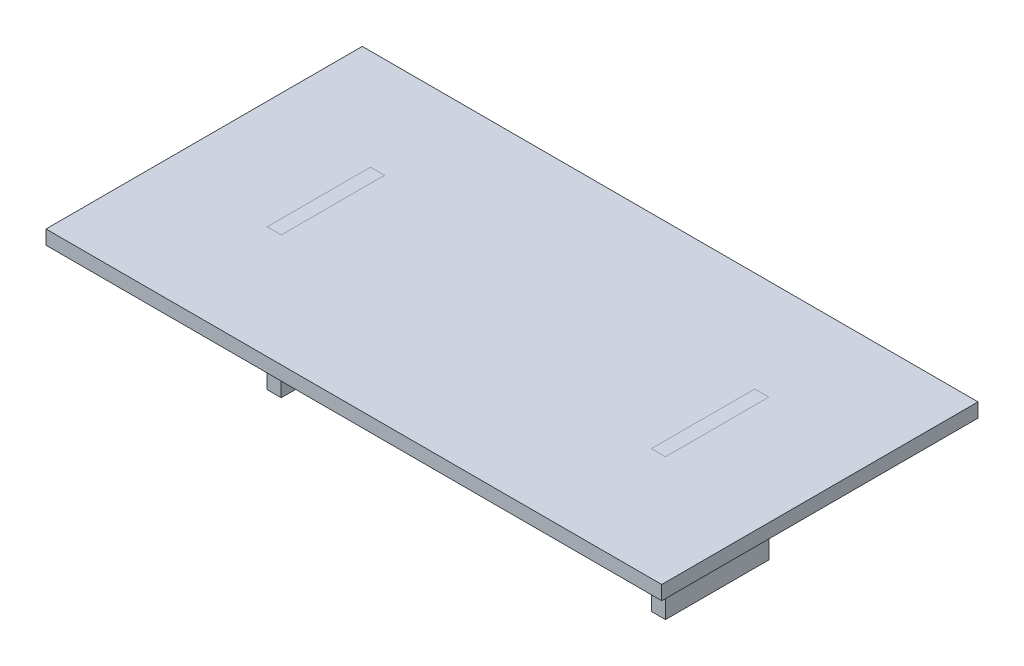
SolidWorks part; units mm, degrees
ref_plane "Front Plane" through (0, 0, 0) normal (0, 0, 1) x (1, 0, 0)
ref_plane "Top Plane" through (0, 0, 0) normal (0, 1, 0) x (1, 0, 0)
ref_plane "Right Plane" through (0, 0, 0) normal (1, 0, 0) x (0, 0, -1)
sketch "Sketch1" plane through (0, 0, 0) normal (0, 1, 0) x (1, 0, 0)
  line L6 (-42.6234, -22.4177) -> (-38.6234, -22.4177)
  line L9 (-38.6234, -22.4177) -> (-42.6234, -22.4177)
  line L10 (-42.6234, 11) -> (-42.6234, -11)
  line L14 (42.1266, 11) -> (42.1266, -11)
  line L15 (23.9842, 12.3255) -> (24.0296, 12.3942) construction
  line L16 (-42.6234, 11) -> (-39.6234, 11)
  line L17 (-42.6234, 11) -> (-42.6234, -11)
  line L18 (-42.6234, -11) -> (-39.6234, -11)
  line L19 (-39.6234, 11) -> (-39.6234, -11)
  line L20 (42.1266, 11) -> (39.1266, 11)
  line L21 (42.1266, 11) -> (42.1266, -11)
  line L22 (42.1266, -11) -> (39.1266, -11)
  line L23 (39.1266, 11) -> (39.1266, -11)
  line L25 (-42.6234, 11) -> (-42.6234, -11)
  line L27 (-65.7484, 19.8706) -> (-65.7484, -22.4177)
  line L29 (42.1266, 11) -> (42.1266, -11)
  line L31 (65.2516, 17.5823) -> (65.2516, -22.4177)
  line L33 (65.2516, 17.5823) -> (65.2516, 32.3706)
  line L34 (65.2516, 32.3706) -> (-65.7484, 32.3706)
  line L35 (-65.7484, 19.8706) -> (-65.7484, 32.3706)
  line L36 (-65.7484, -22.4177) -> (-65.7484, -34.9177)
  line L37 (-65.7484, -34.9177) -> (65.2516, -34.9177)
  line L38 (65.2516, -22.4177) -> (65.2516, -34.9177)
  arc A1 (23.9842, 12.3255) -> (23.8207, 12.4147) centre (23.3776, 11.4078) ccw
  point P0 (0, 0)
  point P29 (-39.6234, 0)
  point P30 (39.1266, 0)
  dimension "D5" = 23.125
  dimension "D9" = 2.2
  dimension "D1" = 84.75
  dimension "D3" = 3
  dimension "D4" = 22
  dimension "D6" = 12.5
extrude "Boss-Extrude1" add sketch "Sketch1" against normal blind 3 contours L37 region at (-0.2484, 0, 1.2929)
extrude "Boss-Extrude2" add sketch "Sketch1<3>" against normal blind 30 separate body contours L19 L16 L10 L18 | L20 L23 L22 L14
sketch "Sketch1<3>" plane through (0, 0, 0) normal (0, 1, 0) x (1, 0, 0) same geometry as "Sketch1"
sketch "Sketch2" plane through (-42.6234, 0, 0) normal (-1, 0, 0) x (0, 0, 1)
  line L0 (0, -19) -> (-5.6569, -24.6569) construction
  line L1 (-11, -30) -> (11, -30) construction
  circle A2 centre (0, -19) radius 3
  circle A3 centre (-5.6569, -24.6569) radius 1.1
  dimension "D1" = 8
  dimension "D5" = 11
  dimension "D2" = 6
  dimension "D3" = 2.2
  dimension "D4" = 45
extrude "Cut-Extrude1" cut sketch "Sketch2" against normal up to surface (3 mm away) contours A2 | A3 region at (-42.6234, -19, 0) up to face at (-39.6234, -15, 0)
sketch "Sketch3" plane through (42.1266, 0, 0) normal (1, 0, 0) x (0, 0, -1)
  circle A1 centre (0, -19) radius 1.5
  dimension "D1" = 3
extrude "Cut-Extrude2" cut sketch "Sketch3" against normal up to surface (3 mm away) up to face at (39.1266, -15, 0)
pattern_circular "CirPattern1" count 4 over 360 about axis through (-42.6234, -19, 0) along (-1, 0, 0) of "Cut-Extrude1"
